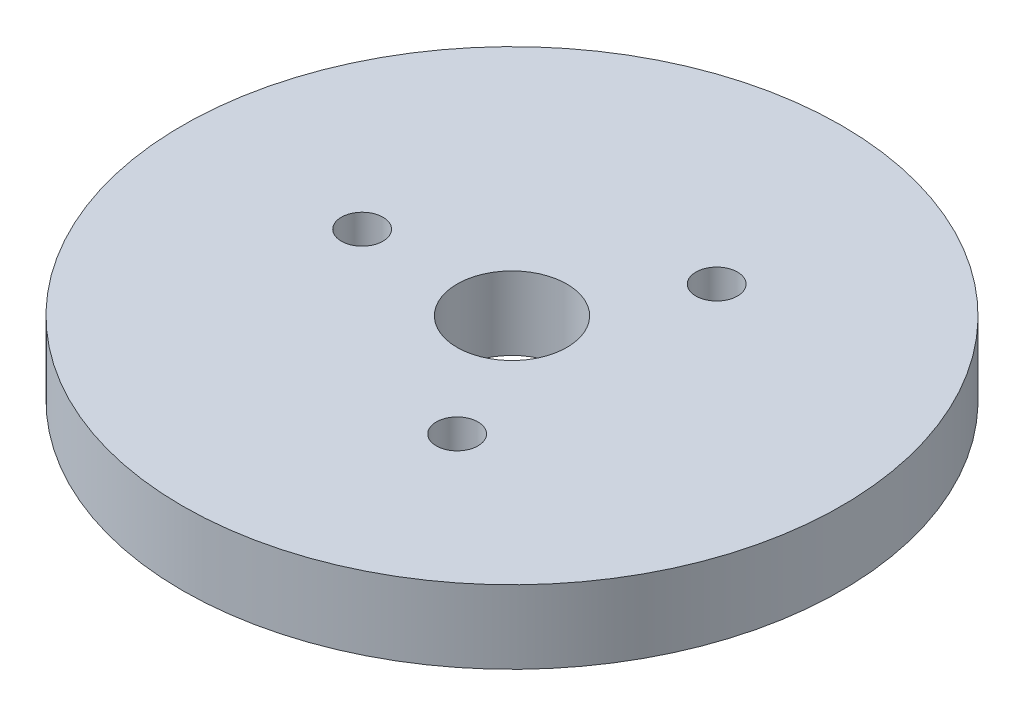
SolidWorks part; units mm, degrees
ref_plane "Front Plane" through (0, 0, 0) normal (0, 0, 1) x (1, 0, 0)
ref_plane "Top Plane" through (0, 0, 0) normal (0, 1, 0) x (1, 0, 0)
ref_plane "Right Plane" through (0, 0, 0) normal (1, 0, 0) x (0, 0, -1)
sketch "Sketch1" plane through (0, 0, 0) normal (0, 1, 0) x (1, 0, 0)
  circle A0 centre (0, 0) radius 90
  dimension "FLANGE_OD" = 180
extrude "Boss-Extrude1" add sketch "Sketch1" along normal blind 20
sketch "Sketch2" plane through (0, 0, 0) normal (0, 1, 0) x (1, 0, 0)
  circle A0 centre (0, 0) radius 15
  dimension "BORE_D" = 30
extrude "Cut-Extrude1" cut sketch "Sketch2" along normal through all
sketch "Sketch3" plane through (0, 20, 0) normal (0, 1, 0) x (1, 0, 0)
  circle A0 centre (0, 0) radius 40.9226 construction
  circle A1 centre (-40.9226, 0) radius 5.6855
  dimension "BOLT_D" = 11.371
  dimension "BOLT_PCD" = 81.8451
extrude "Cut-Extrude2" cut sketch "Sketch3" against normal blind 18.0883
pattern_circular "CirPattern1" count 3 over 360 about axis through (0, 0, 0) along (0, 1, 0) of "Cut-Extrude2"
